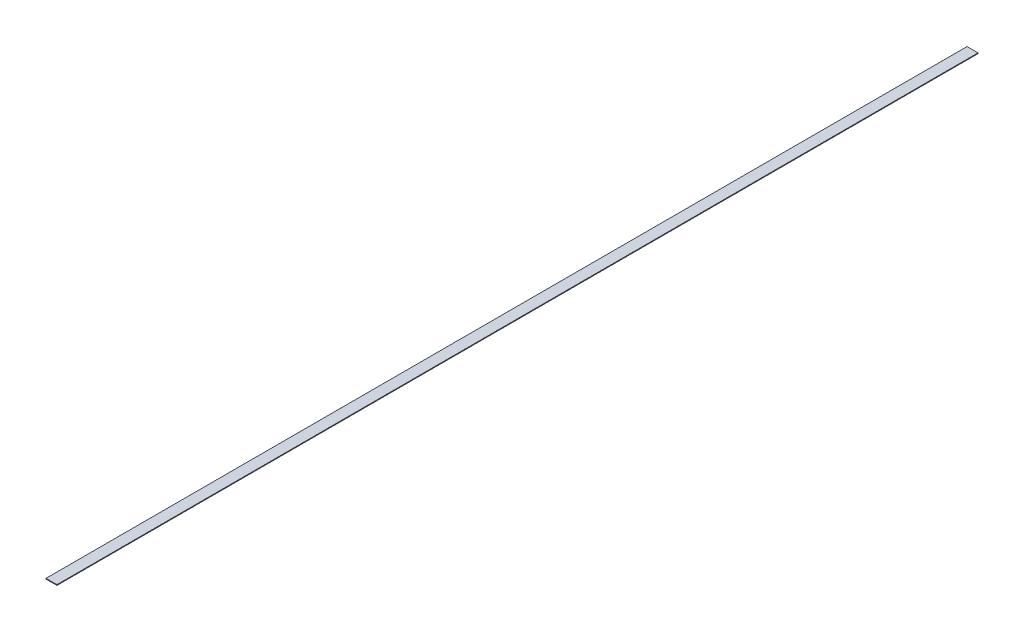
SolidWorks part; units mm, degrees
ref_plane "Front Plane" through (0, 0, 0) normal (0, 0, 1) x (1, 0, 0)
ref_plane "Top Plane" through (0, 0, 0) normal (0, 1, 0) x (1, 0, 0)
ref_plane "Right Plane" through (0, 0, 0) normal (1, 0, 0) x (0, 0, -1)
sketch "Sketch1" plane through (0, 0, 0) normal (0, 0, 1) x (1, 0, 0)
  line L1 (25.4, -1.5875) -> (-25.4, -1.5875)
  line L2 (25.4, -1.5875) -> (25.4, 1.5875)
  line L3 (25.4, 1.5875) -> (-25.4, 1.5875)
  line L4 (-25.4, -1.5875) -> (-25.4, 1.5875)
  line L5 (25.4, -1.5875) -> (-25.4, 1.5875) construction
  line L6 (25.4, 1.5875) -> (-25.4, -1.5875) construction
  circle A0 centre (0, 0) radius 3.175 construction
  dimension "D1" = 6.35
  dimension "D2" = 50.8
  dimension "D3" = 3.175
extrude "Extrude1" add sketch "Sketch1" along normal blind 4267.2
sketch "Sketch2" [suppressed] plane through (0, 0, 0) normal (0, 0, -1) x (-1, 0, 0)
  point P0 (0, 0)
sketch "Sketch3" [suppressed] plane through (0, 0, 4572) normal (0, 0, 1) x (1, 0, 0)
  point P0 (0, 0)
sketch "Sketch4" plane through (0, 0, 0) normal (0, 0, -1) x (-1, 0, 0)
  point P0 (0, 0)
sketch "Sketch5" plane through (0, 0, 4267.2) normal (0, 0, 1) x (1, 0, 0)
  point P0 (0, 0)
